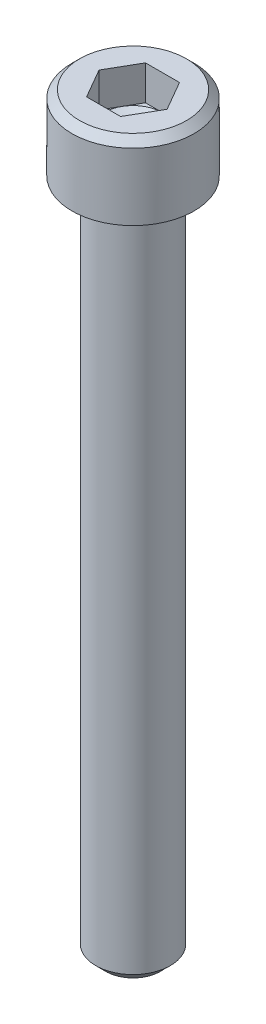
SolidWorks part; units mm, degrees
material "Alloy Steel"
ref_plane "Front Plane" through (0, 0, 0) normal (0, 0, 1) x (1, 0, 0)
ref_plane "Top Plane" through (0, 0, 0) normal (0, 1, 0) x (1, 0, 0)
ref_plane "Right Plane" through (0, 0, 0) normal (1, 0, 0) x (0, 0, -1)
sketch "Sketch1" plane through (0, 0, 0) normal (0, 0, 1) x (1, 0, 0)
  line L0 (2.8702, 3.5052) -> (0, 3.5052)
  line L1 (0, 3.5052) -> (0, 0)
  line L2 (0, 0) -> (2.8702, 0)
  line L3 (2.8702, 0) -> (2.8702, 3.5052)
  line L4 (0, 3.5052) -> (0, 0) construction
revolve "Revolve1" add sketch "Sketch1" angle 360 about L4 reverse direction yes
sketch "Sketch2" plane through (0, 0, 0) normal (0, -1, 0) x (1, 0, 0)
  circle A0 centre (0, 0) radius 1.7526
extrude "Boss-Extrude1" add sketch "Sketch2" along normal blind 31.75
sketch "Sketch3" plane through (0, 3.5052, 0) normal (0, 1, 0) x (-1, 0, 0)
  line L0 (-0.7992, 1.3843) -> (-1.5985, 0)
  line L1 (-1.5985, 0) -> (-0.7992, -1.3843)
  line L2 (-0.7992, -1.3843) -> (0.7992, -1.3843)
  line L3 (0.7992, -1.3843) -> (1.5985, 0)
  line L4 (1.5985, 0) -> (0.7992, 1.3843)
  line L5 (0.7992, 1.3843) -> (-0.7992, 1.3843)
extrude "Cut-Extrude1" cut sketch "Sketch3" against normal blind 1.6256
sketch "Sketch4" plane through (0, 0, 0) normal (0, 0, 1) x (1, 0, 0)
  line L0 (1.3843, 1.8796) -> (0, 1.8796)
  line L1 (0, 1.8796) -> (0, 1.0804)
  line L2 (0, 1.0804) -> (1.3843, 1.8796)
  line L3 (0, 1.8796) -> (0, 1.0803) construction
revolve "Cut-Revolve1" cut sketch "Sketch4" angle 360 about L3 reverse direction yes
chamfer "Chamfer1" distance 0.4724 angle 45 1 edges at (0, -31.75, -1.7526)
chamfer "Chamfer2" distance 0.3556 angle 45 1 edges at (0, 3.5052, -2.8702)
fillet "Fillet1" radius 0.254 1 edges at (0, 0, -1.7526) tangent propagation no
